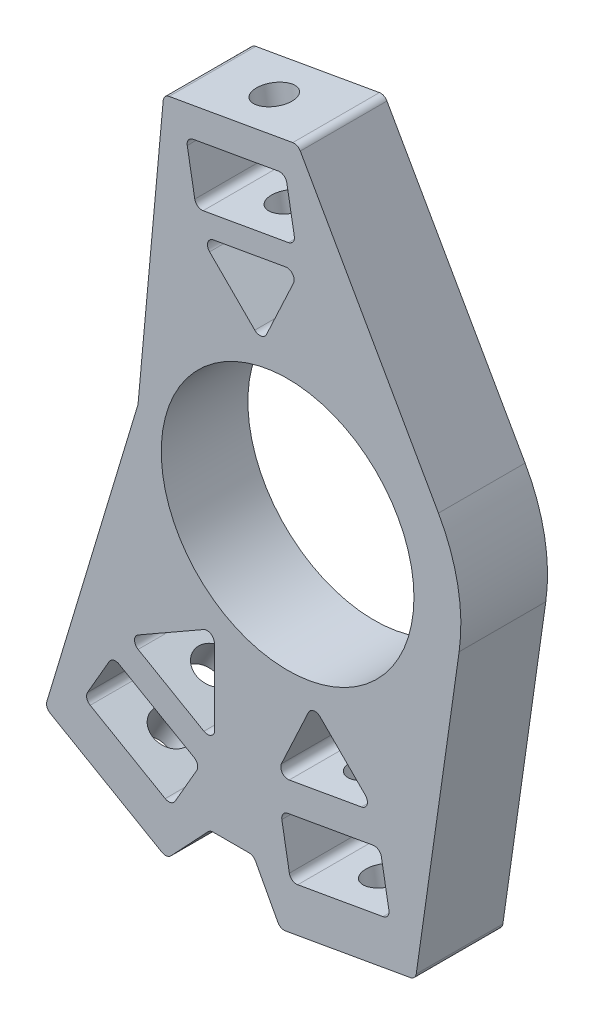
SolidWorks part; units mm, degrees
ref_plane "Front Plane" through (0, 0, 0) normal (0, 0, 1) x (1, 0, 0)
ref_plane "Top Plane" through (0, 0, 0) normal (0, 1, 0) x (1, 0, 0)
ref_plane "Right Plane" through (0, 0, 0) normal (1, 0, 0) x (0, 0, -1)
sketch "Sketch1" plane through (0, 0, 0) normal (0, 0, 1) x (1, 0, 0)
  circle A0 centre (0, 0) radius 57.5 construction
  dimension "D1" = 115
sketch "Sketch2" plane through (0, 0, 0) normal (0, 0, 1) x (1, 0, 0)
  line L0 (0, 0) -> (-81.4302, 0) construction
  line L1 (0, 0) -> (-7.2932, 41.3619) construction
  line L2 (0, 0) -> (7.8142, -44.3163) construction
  line L3 (0, 0) -> (-24, -41.5692) construction
  line L4 (1.4128, 46.2818) -> (20.8945, 11.8077)
  line L5 (-17.1569, 43.0074) -> (-20.9128, 1.9113)
  line L6 (23.759, -3.3925) -> (17.7138, -45.7299)
  line L7 (-21.1659, -11.314) -> (-1.0049, -49.0305)
  line L8 (-20.1088, 6.0528) -> (-33.5756, -38.6869)
  line L9 (-16.7161, -48.4208) -> (15.2963, -14.3883)
  line L10 (0, 0) -> (8.2822, -30.9096) construction
  line L11 (17.7138, -45.7299) -> (-1.0049, -49.0305)
  line L12 (-16.7161, -48.4208) -> (-33.5756, -38.6869)
  line L13 (1.4128, 46.2818) -> (-17.1569, 43.0074)
  line L14 (-10.7316, -42.0587) -> (-4.7316, -42.0587)
  circle A0 centre (0, 0) radius 21
  circle A1 centre (-7.2932, 41.3619) radius 6 construction
  circle A2 centre (7.8142, -44.3163) radius 6 construction
  circle A5 centre (7.8142, -44.3163) radius 10 construction
  circle A7 centre (-7.2932, 41.3619) radius 10 construction
  circle A8 centre (8.2822, -30.9096) radius 6 construction
  circle A9 centre (-24, -41.5692) radius 10 construction
  circle A10 centre (0, 0) radius 17.5
  circle A11 centre (0, 0) radius 24
  dimension "D1" = 42
  dimension "D2" = 80
  dimension "D3" = 12
  dimension "D7" = 12
  dimension "D8" = 12
  dimension "D11" = 48
  dimension "D12" = 48
  dimension "D13" = 20
  dimension "D14" = 6
  dimension "D15" = 20
  dimension "D17" = 20
  dimension "D18" = 35
  dimension "D4" = 42
  dimension "D5" = 45
  dimension "D6" = 100
  dimension "D9" = 75
  dimension "D10" = 60
  dimension "D16" = 32
  dimension "D19" = 90
extrude "Boss-Extrude1" add sketch "Sketch2" along normal blind 12 contours A7 A1 | A1 | A5 A8 | A2 | A8 A5 A2 | A5 A8 | A11 L4 L13 L5 | A11 L5 L8 A0 L9 | A10 | A0 A10 | L8 A11 L9 A0 L5 | A0 L8 L5 | A11 L8 L12 L9 L7 | A11 L7 L9 | A11 L9 L7 L11 L6 | L9 L14 L7 region at (-4.5656, 31.7303, 0) region at (22.5843, 5.9399, 0) region at (9.4394, -33.8152, 0) region at (-20.6361, 4.0064, 0) region at (-20.864, 2.9713, 0) region at (-20.8738, -30.9766, 0) region at (-6.3625, -27.2158, 0) region at (-20.032, 3.8891, 0) region at (-7.4563, -40.703, 0) region at (0, 0, 0)
extrude "Cut-Extrude1" cut sketch "Sketch2<5>" along normal through all contours A10 region at (0, 0, 0)
sketch "Sketch2<5>" plane through (0, 0, 0) normal (0, 0, 1) x (1, 0, 0) same geometry as "Sketch2"
sketch "Sketch4" plane through (0, 0, 0) normal (0, 0, -1) x (-1, 0, 0)
  line L0 (-1.4128, 46.2818) -> (17.1569, 43.0074)
  line L1 (17.1569, 43.0074) -> (20.7199, 4.0226)
  line L2 (20.7199, 4.0226) -> (33.5756, -38.6869)
  line L3 (33.5756, -38.6869) -> (16.7161, -48.4208)
  line L4 (16.7161, -48.4208) -> (10.7316, -42.0587)
  line L5 (10.7316, -42.0587) -> (4.7316, -42.0587)
  line L6 (4.7316, -42.0587) -> (1.0049, -49.0305)
  line L7 (1.0049, -49.0305) -> (-17.7138, -45.7299)
  line L8 (-17.7138, -45.7299) -> (-23.759, -3.3925)
  line L9 (-1.4128, 46.2818) -> (-20.8945, 11.8077)
  line L10 (0, 0) -> (25.1458, -43.5539) construction
  line L11 (0, 0) -> (-8.3544, -47.3802) construction
  line L12 (0, 0) -> (7.8721, 44.6446) construction
  line L13 (27.342, -35.3577) -> (16.9497, -41.3577)
  line L14 (27.708, -33.9917) -> (24.708, -28.7955)
  line L15 (15.5837, -40.9917) -> (12.5837, -35.7955)
  line L16 (23.342, -28.4295) -> (12.9497, -34.4295)
  line L17 (28.208, -34.8577) -> (12.0837, -34.9295) construction
  line L18 (16.0837, -41.8577) -> (24.208, -27.9295) construction
  line L19 (24.208, -27.9295) -> (22.208, -24.4654) construction
  line L20 (12.0837, -34.9295) -> (10.0837, -31.4654) construction
  line L21 (20.7002, -25.3359) -> (11.5914, -30.5949)
  line L22 (10.0914, -29.7244) -> (10.1382, -19.2874)
  line L23 (11.6343, -18.4236) -> (20.6963, -23.6016)
  line L24 (-1.4037, -42.5132) -> (-13.2214, -40.4295)
  line L25 (-0.2452, -41.7021) -> (0.7967, -35.7932)
  line L26 (-14.0325, -39.271) -> (-12.9906, -33.3622)
  line L27 (-0.0145, -34.6348) -> (-11.8322, -32.551)
  line L28 (-0.4189, -42.6869) -> (-12.817, -32.3773) construction
  line L29 (-14.2062, -40.2558) -> (0.9703, -34.8084) construction
  line L30 (-12.817, -32.3773) -> (-12.1224, -28.4381) construction
  line L31 (0.9703, -34.8084) -> (1.6649, -30.8692) construction
  line L32 (-10.2309, -28.7716) -> (-0.2266, -30.5357)
  line L33 (0.8535, -29.1284) -> (-2.8887, -21.1004)
  line L34 (-4.5023, -20.8159) -> (-10.7645, -27.0798)
  line L35 (11.6971, 31.785) -> (-0.1206, 33.8688)
  line L36 (12.8556, 32.5962) -> (13.8975, 38.505)
  line L37 (-0.9317, 35.0273) -> (0.1102, 40.9361)
  line L38 (13.0863, 39.6635) -> (1.2686, 41.7473)
  line L39 (12.6819, 31.6114) -> (0.2838, 41.9209) construction
  line L40 (-1.1054, 34.0425) -> (14.0711, 39.4898) construction
  line L41 (-1.1054, 34.0425) -> (-1.6263, 31.088) construction
  line L42 (12.6819, 31.6114) -> (12.161, 28.657) construction
  line L43 (-0.8149, 29.3472) -> (2.9273, 21.3192)
  line L44 (4.5409, 21.0347) -> (10.8031, 27.2987)
  line L45 (10.2695, 28.9905) -> (0.2652, 30.7545)
  arc A0 (-20.8945, 11.8077) -> (-23.759, -3.3925) centre (0, 0) ccw
  arc A1 (-20.8945, 11.8077) -> (-23.759, -3.3925) centre (0, 0) ccw construction
  arc A2 (-0.1206, 33.8688) -> (-0.9317, 35.0273) centre (0.0531, 34.8536) cw
  arc A3 (20.7002, -25.3359) -> (20.6963, -23.6016) centre (20.2002, -24.4699) ccw
  arc A4 (11.5914, -30.5949) -> (10.0914, -29.7244) centre (11.0914, -29.7289) cw
  arc A5 (10.1382, -19.2874) -> (11.6343, -18.4236) centre (11.1382, -19.2918) cw
  arc A6 (23.342, -28.4295) -> (24.708, -28.7955) centre (23.842, -29.2955) cw
  arc A7 (27.708, -33.9917) -> (27.342, -35.3577) centre (26.842, -34.4917) cw
  arc A8 (15.5837, -40.9917) -> (16.9497, -41.3577) centre (16.4497, -40.4917) ccw
  arc A9 (12.5837, -35.7955) -> (12.9497, -34.4295) centre (13.4497, -35.2955) cw
  arc A10 (0.1102, 40.9361) -> (1.2686, 41.7473) centre (1.095, 40.7625) cw
  arc A11 (13.8975, 38.505) -> (13.0863, 39.6635) centre (12.9127, 38.6787) ccw
  arc A12 (12.8556, 32.5962) -> (11.6971, 31.785) centre (11.8708, 32.7698) cw
  arc A13 (10.8031, 27.2987) -> (10.2695, 28.9905) centre (10.0959, 28.0057) ccw
  arc A14 (-0.8149, 29.3472) -> (0.2652, 30.7545) centre (0.0915, 29.7697) cw
  arc A15 (2.9273, 21.3192) -> (4.5409, 21.0347) centre (3.8337, 21.7417) ccw
  arc A16 (-0.0145, -34.6348) -> (0.7967, -35.7932) centre (-0.1881, -35.6196) cw
  arc A17 (-0.2452, -41.7021) -> (-1.4037, -42.5132) centre (-1.23, -41.5284) cw
  arc A18 (-13.2214, -40.4295) -> (-14.0325, -39.271) centre (-13.0477, -39.4447) cw
  arc A19 (-12.9906, -33.3622) -> (-11.8322, -32.551) centre (-12.0058, -33.5358) cw
  arc A20 (-4.5023, -20.8159) -> (-2.8887, -21.1004) centre (-3.7951, -21.5229) cw
  arc A21 (-0.2266, -30.5357) -> (0.8535, -29.1284) centre (-0.0529, -29.5509) ccw
  arc A22 (-10.2309, -28.7716) -> (-10.7645, -27.0798) centre (-10.0573, -27.7868) cw
  point P28 (20.1458, -34.8936)
  point P46 (10.1458, -17.5731)
  point P60 (-6.6179, -37.5321)
  point P64 (6.4829, 36.7662)
  point P95 (3.5308, 20.0244)
  point P110 (-3.4923, -19.8056)
  dimension "D1" = 6
  dimension "D6" = 1
  dimension "D7" = 1
  dimension "D11" = 4
  dimension "D13" = 14
  dimension "D18" = 1
  dimension "D19" = 1
  dimension "D2" = 8
  dimension "D3" = 14
  dimension "D4" = 4
  dimension "D5" = 12
  dimension "D8" = 14
  dimension "D9" = 8
  dimension "D10" = 6
  dimension "D12" = 10
  dimension "D14" = 8
  dimension "D15" = 4
  dimension "D16" = 3
  dimension "D17" = 10
extrude "Cut-Extrude2" cut sketch "Sketch4" against normal through all contours A9 L15 A8 L13 A7 L14 A6 L16 | A22 L32 A21 L33 A20 L34 | A19 L26 A18 L24 A17 L25 A16 L27 | L43 A15 L44 A13 L45 A14 | A12 L36 A11 L38 A10 L37 A2 L35 | L23 A3 L21 A4 L22 A5 region at (-20.1458, -34.8936, 0) region at (6.6179, -37.5321, 0) region at (4.6448, -26.3417, 0) region at (-6.4829, 36.7662, 0) region at (-4.6833, 26.5605, 0)
fillet "Fillet2" radius 1 8 edges at (17.7138, -45.7299, 6) (-1.0049, -49.0305, 6) (-10.7316, -42.0587, 6) (-4.7316, -42.0587, 6) (-16.7161, -48.4208, 6) (-33.5756, -38.6869, 6) (-17.1569, 43.0074, 6) (1.4128, 46.2818, 6)
sketch "Sketch5" plane through (8.3544, -47.3802, 0) normal (0.1736, -0.9848, 0) x (0.9848, 0.1736, 0)
  line L0 (-8.7789, 12) -> (8.7789, 0) construction
  line L1 (8.7789, 12) -> (-8.7789, 0) construction
  circle A0 centre (0, 6) radius 2.5
  dimension "D1" = 5
extrude "Cut-Extrude3" cut sketch "Sketch5" against normal blind 20
sketch "Sketch6" plane through (-25.1458, -43.5539, 0) normal (-0.5, -0.866, 0) x (0.866, -0.5, 0)
  line L0 (-8.942, 12) -> (8.942, 0) construction
  circle A0 centre (0, 6) radius 2.5
  dimension "D1" = 5
extrude "Cut-Extrude4" cut sketch "Sketch6" against normal blind 20
sketch "Sketch7" plane through (-7.8721, 44.6446, 0) normal (-0.1736, 0.9848, 0) x (0.9848, 0.1736, 0)
  line L0 (-8.6638, 0) -> (8.721, -12)
  circle A0 centre (0.0286, -6) radius 2.5
  dimension "D1" = 5
extrude "Cut-Extrude5" cut sketch "Sketch7" against normal blind 20 contours L0 A0 | L0 A0 region at (-7.2503, 44.7542, 5.1268) region at (-8.4375, 44.5449, 6.8732)
